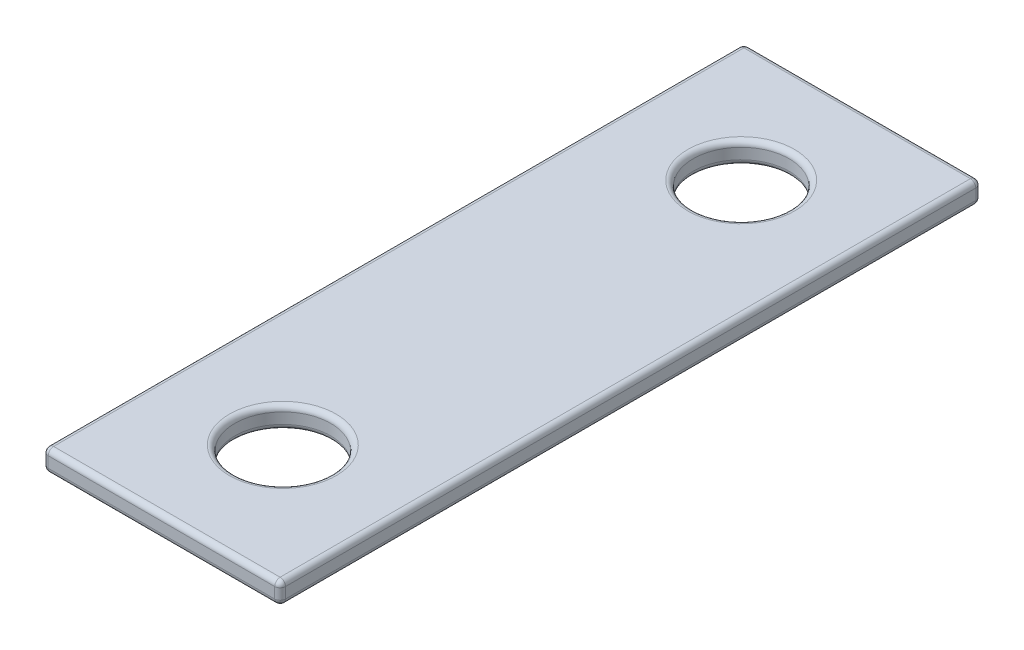
SolidWorks part; units mm, degrees
material "AISI 304"
ref_plane "Front Plane" through (0, 0, 0) normal (0, 0, 1) x (1, 0, 0)
ref_plane "Top Plane" through (0, 0, 0) normal (0, 1, 0) x (1, 0, 0)
ref_plane "Right Plane" through (0, 0, 0) normal (1, 0, 0) x (0, 0, -1)
sketch "Sketch1" plane through (0, 0, 0) normal (0, 1, 0) x (1, 0, 0)
  line L0 (-1.1358, -8.8539) -> (-1.1358, 7.6561)
  line L1 (-6.7238, 7.6561) -> (-1.1358, 7.6561)
  line L2 (-6.7238, 7.6561) -> (-6.7238, -8.8539)
  line L3 (-6.7238, -8.8539) -> (-1.1358, -8.8539)
  circle A0 centre (-3.9298, 4.7986) radius 1.1303
  circle A1 centre (-3.9298, -5.9964) radius 1.1303
  dimension "D8" = 2.2606
  dimension "D10" = 2.2606
  dimension "D11" = 2.794
  dimension "D2" = 2.794
  dimension "D4" = 10.795
  dimension "D6" = 2.794
extrude "Boss-Extrude1" add sketch "Sketch1" along normal blind 0.508
fillet "Fillet1" radius 0.127 16 edges at (-1.1358, 0.254, -7.6561) (-6.7238, 0.254, -7.6561) (-3.9298, 0.508, -7.6561) (-3.9298, 0, -7.6561) (-6.7238, 0, 0.5989) (-1.1358, 0, 0.5989) (-1.1358, 0.508, 0.5989) (-6.7238, 0.508, 0.5989) (-3.9298, 0.508, 8.8539) (-3.9298, 0, 8.8539) (-6.7238, 0.254, 8.8539) (-1.1358, 0.254, 8.8539) (-3.9298, 0, -3.6683) (-3.9298, 0.508, -3.6683) (-3.9298, 0, 7.1267) (-3.9298, 0.508, 7.1267)
